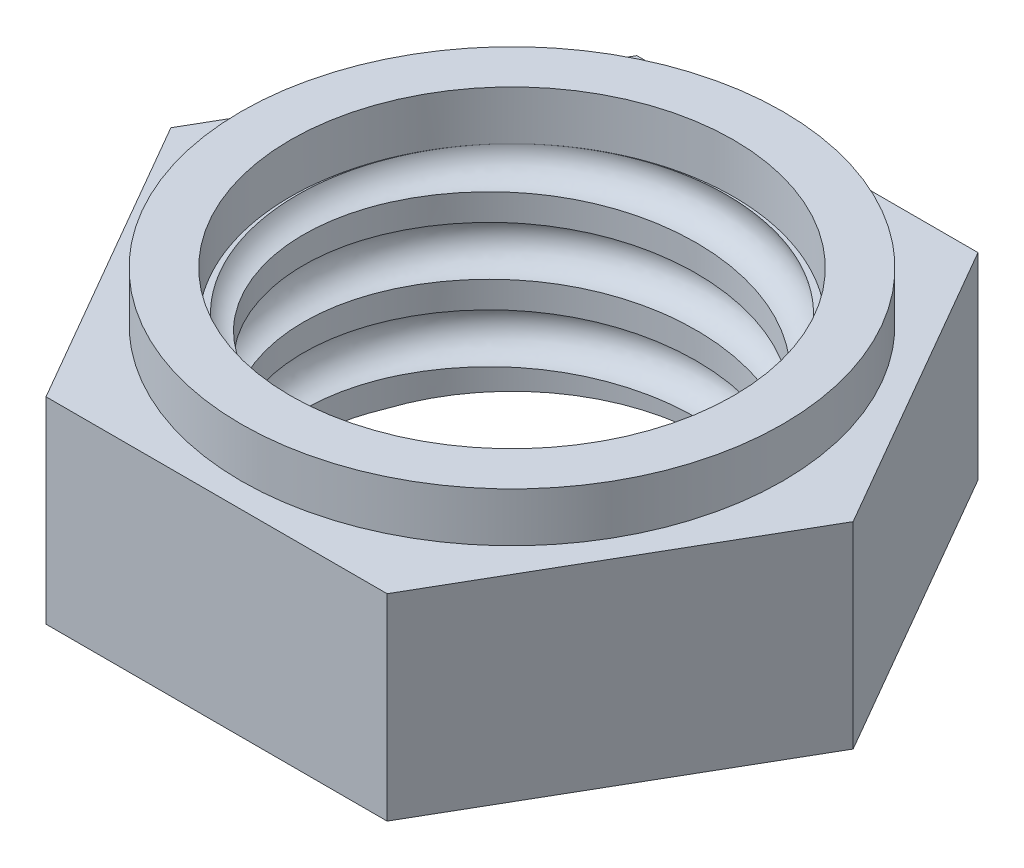
SolidWorks part; units mm, degrees
ref_plane "Front Plane" through (0, 0, 0) normal (0, 0, 1) x (1, 0, 0)
ref_plane "Top Plane" through (0, 0, 0) normal (0, 1, 0) x (1, 0, 0)
ref_plane "Right Plane" through (0, 0, 0) normal (1, 0, 0) x (0, 0, -1)
sketch "Sketch1" plane through (0, 0, 0) normal (0, 1, 0) x (1, 0, 0)
  line L1 (0.8799, 1.524) -> (-0.8799, 1.524)
  line L2 (-0.8799, 1.524) -> (-1.7598, 0)
  line L3 (-1.7598, 0) -> (-0.8799, -1.524)
  line L4 (-0.8799, -1.524) -> (0.8799, -1.524)
  line L5 (0.8799, -1.524) -> (1.7598, 0)
  line L6 (1.7598, 0) -> (0.8799, 1.524)
  circle A0 centre (0, 0) radius 1.524 construction
  dimension "D1" = 3.048
extrude "Boss-Extrude1" add sketch "Sketch1" along normal blind 1.016
sketch "Sketch2" plane through (0, 1.016, 0) normal (0, 1, 0) x (1, 0, 0)
  circle A0 centre (0, 0) radius 1.016
  dimension "D1" = 2.032
extrude "Cut-Extrude1" cut sketch "Sketch2" against normal through all
sketch "Sketch3" plane through (0, 1.016, 0) normal (0, 1, 0) x (1, 0, 0)
  circle A0 centre (0, 0) radius 1.016
  dimension "D1" = 2.032
curve "Helix/Spiral1" pitch 0.3908 height 5.08 turns 13
sketch "Sketch4" plane through (0, 0, 0) normal (0, 0, 1) x (1, 0, 0)
  circle A0 centre (-1.016, -0.4982) radius 0.127
  dimension "D1" = 0.254
sweep "Cut-Sweep1" cut profiles "Sketch4" path "Helix/Spiral1" align with end faces yes
sketch "Sketch5" plane through (0, 1.016, 0) normal (0, 1, 0) x (1, 0, 0)
  circle A0 centre (0, 0) radius 1.397
  circle A1 centre (0, 0) radius 1.143
  dimension "D1" = 2.794
  dimension "D2" = 2.286
extrude "Boss-Extrude2" add sketch "Sketch5" along normal blind 0.254
